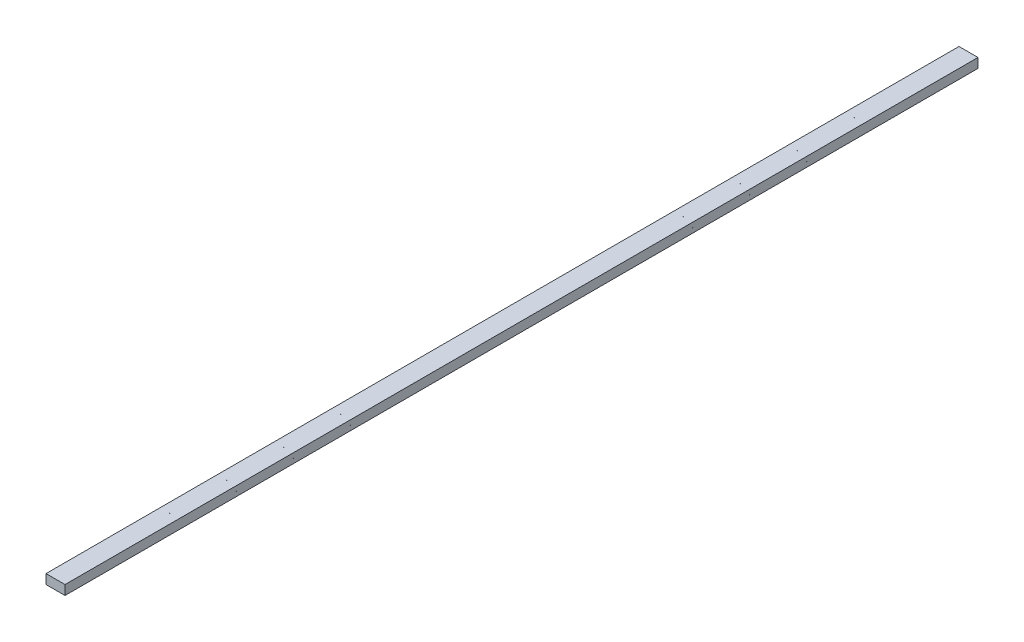
SolidWorks part; units mm, degrees
material "Pine"
ref_plane "Front Plane" through (0, 0, 0) normal (0, 0, 1) x (1, 0, 0)
ref_plane "Top Plane" through (0, 0, 0) normal (0, 1, 0) x (1, 0, 0)
ref_plane "Right Plane" through (0, 0, 0) normal (1, 0, 0) x (0, 0, -1)
sketch "Sketch1" plane through (0, 0, 0) normal (0, 0, 1) x (1, 0, 0)
  line L1 (0, 0) -> (101.6, 0)
  line L2 (0, 0) -> (0, 50.8)
  line L3 (0, 50.8) -> (101.6, 50.8)
  line L4 (101.6, 0) -> (101.6, 50.8)
  dimension "D1" = 101.6
  dimension "D2" = 50.8
extrude "Boss-Extrude1" add sketch "Sketch1" along normal blind 4876.8
sketch "Sketch2" plane through (0, 50.8, 0) normal (0, 1, 0) x (1, 0, 0)
  line L0 (50.8, 0) -> (50.8, -304.8) construction
  line L1 (101.6, 0) -> (0, 0) construction
  line L2 (0, 0) -> (0, -4876.8)
  circle A0 centre (50.8, -304.8) radius 0.8763
  dimension "D2" = 1.7526
  dimension "D1" = 304.8
extrude "Cut-Extrude1" cut sketch "Sketch2" against normal up to surface (50.8 mm away) contours A0 region at (50.8, 50.8, 304.8) up to face at (50.8, 0, 2438.4)
pattern_linear "LPattern1" count 15 spacing 304.8 along (0, 0, 1) of "Cut-Extrude1"
sketch "Sketch3" plane through (0, 50.8, 0) normal (0, 1, 0) x (1, 0, 0)
  line L0 (50.8, 0) -> (50.8, -50.8) construction
  line L1 (101.6, 0) -> (0, 0) construction
  line L2 (101.6, -2438.4) -> (0, -2438.4) construction
  line L3 (101.6, -4876.8) -> (101.6, 0) construction
  line L4 (0, -4876.8) -> (0, 0) construction
  circle A0 centre (50.8, -50.8) radius 0.8763
  circle A1 centre (50.8, -4724.4) radius 0.8763
  circle A2 centre (50.8, -101.6) radius 0.8763
  circle A3 centre (50.8, -152.4) radius 0.8763
  circle A4 centre (50.8, -4775.2) radius 0.8763
  circle A5 centre (50.8, -4826) radius 0.8763
  dimension "D2" = 1.7526
  dimension "D1" = 50.8
  dimension "D3" = 3
extrude "Cut-Extrude2" cut sketch "Sketch3" against normal up to surface (50.8 mm away) up to face at (50.8, 0, 4572.8763)
sketch "Sketch4" plane through (0, 0, 4876.8) normal (0, 0, 1) x (1, 0, 0)
  line L0 (0, 50.8) -> (101.6, 0) construction
  line L1 (101.6, 50.8) -> (0, 0) construction
  circle A0 centre (50.8, 25.4) radius 0.8763
  dimension "D1" = 1.7526
extrude "Cut-Extrude3" cut sketch "Sketch4" against normal up to surface (4876.8 mm away) up to face at (50.8, 25.4, 0)
sketch "Sketch6" plane through (0, 0, 0) normal (-1, 0, 0) x (0, 0, 1)
  line L0 (0, 25.4) -> (304.8, 25.4) construction
  line L1 (0, 50.8) -> (0, 0) construction
  circle A0 centre (304.8, 25.4) radius 0.8763
  circle A1 centre (609.6, 25.4) radius 0.8763
  circle A2 centre (914.4, 25.4) radius 0.8763
  circle A3 centre (1219.2, 25.4) radius 0.8763
  circle A4 centre (1524, 25.4) radius 0.8763
  circle A5 centre (1828.8, 25.4) radius 0.8763
  circle A6 centre (2133.6, 25.4) radius 0.8763
  circle A7 centre (2438.4, 25.4) radius 0.8763
  circle A8 centre (2743.2, 25.4) radius 0.8763
  circle A9 centre (3048, 25.4) radius 0.8763
  circle A10 centre (3352.8, 25.4) radius 0.8763
  circle A11 centre (3657.6, 25.4) radius 0.8763
  circle A12 centre (3962.4, 25.4) radius 0.8763
  circle A13 centre (4267.2, 25.4) radius 0.8763
  circle A14 centre (4572, 25.4) radius 0.8763
  dimension "D2" = 1.7526
  dimension "D1" = 304.8
  dimension "D3" = 15
extrude "Cut-Extrude4" cut sketch "Sketch6" against normal up to surface (101.6 mm away) up to face at (101.6, 25.4, 2438.4)
sketch "Sketch7" plane through (0, 0, 0) normal (-1, 0, 0) x (0, 0, 1)
  line L0 (0, 25.4) -> (50.8, 25.4) construction
  line L1 (0, 50.8) -> (0, 0) construction
  line L2 (2438.4, 0) -> (2438.4, 50.8) construction
  line L3 (4876.8, 0) -> (0, 0) construction
  line L4 (4876.8, 50.8) -> (0, 50.8) construction
  circle A0 centre (50.8, 25.4) radius 0.8763
  circle A1 centre (101.6, 25.4) radius 0.8763
  circle A2 centre (152.4, 25.4) radius 0.8763
  circle A3 centre (4724.4, 25.4) radius 0.8763
  circle A4 centre (4775.2, 25.4) radius 0.8763
  circle A5 centre (4826, 25.4) radius 0.8763
  dimension "D1" = 1.7526
  dimension "D2" = 50.8
  dimension "D3" = 3
extrude "Cut-Extrude5" cut sketch "Sketch7" against normal up to surface (101.6 mm away) up to face at (101.6, 25.4, 4572.8763)
equation "\"length\" = 1219.2 * 4"
equation "\"D1@Boss-Extrude1\"=\"length\""
equation "\"D1@LPattern1\" = \"length\" / 304.8 - 1"
equation "\"D3@Sketch6\"=\"length\" / 304.8 - 1"
